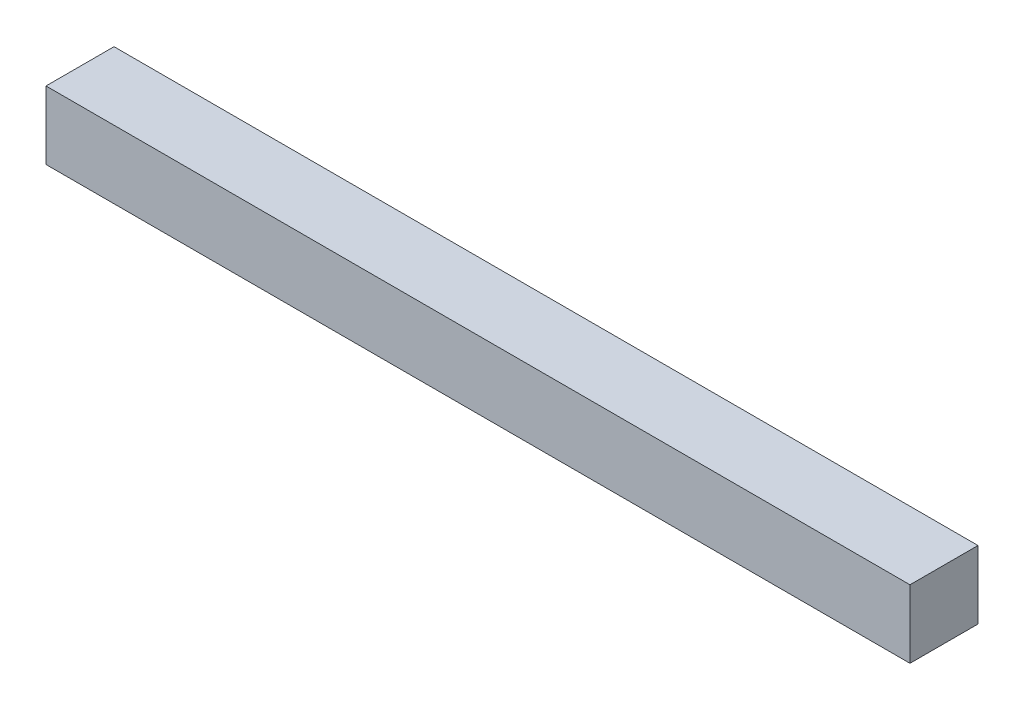
SolidWorks part; units mm, degrees
ref_plane "Plan de face" through (0, 0, 0) normal (0, 0, 1) x (1, 0, 0)
ref_plane "Plan de dessus" through (0, 0, 0) normal (0, 1, 0) x (1, 0, 0)
ref_plane "Plan de droite" through (0, 0, 0) normal (1, 0, 0) x (0, 0, -1)
sketch "Esquisse1" plane through (0, 0, 0) normal (0, 0, 1) x (1, 0, 0)
  line L1 (-14.7006, 5.1608) -> (112.2994, 5.1608)
  line L2 (-14.7006, 5.1608) -> (-14.7006, -4.8392)
  line L3 (-14.7006, -4.8392) -> (112.2994, -4.8392)
  line L4 (112.2994, 5.1608) -> (112.2994, -4.8392)
  dimension "D1" = 10
  dimension "D2" = 127
extrude "Boss.-Extru.1" add sketch "Esquisse1" along normal blind 10 contours L2 L3 L4 L1
equation "\"D2@Esquisse1\"=\"LargeurGauche\" - 23"
equation "\"EpaisseurPlaque\"= 3"
equation "\"ProfondeurBoite\"=460"
equation "\"LongueurSyphon\"=170"
equation "\"LargeurSyphon\"=120"
equation "\"HauteurCoteDroit\"= 490"
equation "\"HauteurCoteGauche\"= 540"
equation "\"HauteurSolSyphon\"= 300"
equation "\"HauteurSyphon\"=\"HauteurCoteGauche\"-\"HauteurSolSyphon\""
equation "\"LargeurDroite\"=10"
equation "\"LargeurGauche\"=150"
equation "\"LargeurBoite\"= \"LargeurDroite\" + \"LargeurGauche\" + \"LargeurSyphon\""
